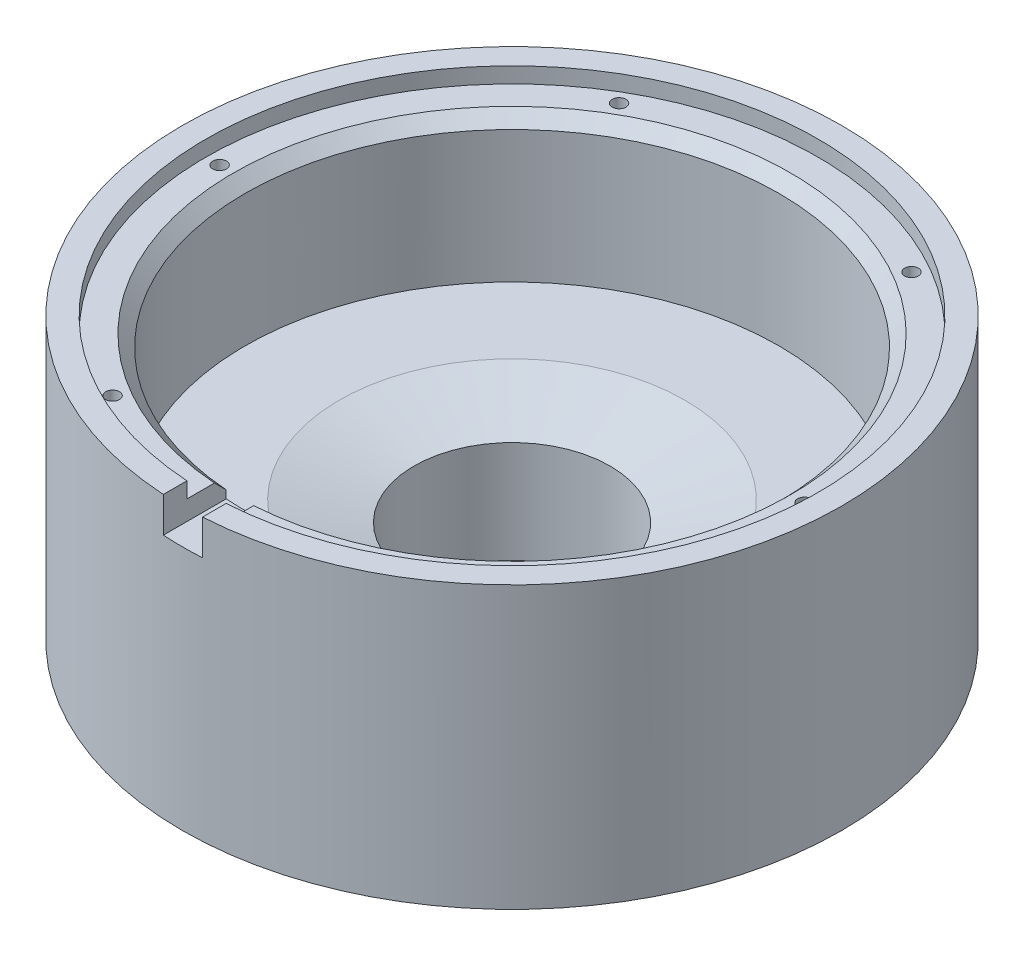
SolidWorks part; units mm, degrees
material "1060 Alloy"
ref_plane "Front Plane" through (0, 0, 0) normal (0, 0, 1) x (1, 0, 0)
ref_plane "Top Plane" through (0, 0, 0) normal (0, 1, 0) x (1, 0, 0)
ref_plane "Right Plane" through (0, 0, 0) normal (1, 0, 0) x (0, 0, -1)
sketch "Sketch7" plane through (0, 0, 0) normal (0, 0, 1) x (1, 0, 0)
  line L0 (0, -30.2319) -> (0, 30.2319) construction
  line L1 (-42.0375, 21.59) -> (-39.0375, 21.59)
  line L2 (-39.0375, 21.59) -> (-39.0375, 19.59)
  line L3 (-39.0375, 19.59) -> (-34.0375, 19.59)
  line L4 (-34.0375, 19.59) -> (-34.0375, 1.25)
  line L7 (-22.0375, 1.25) -> (-34.0375, 1.25)
  line L8 (-12.5, -1.25) -> (-12.5, -14.25)
  line L9 (-12.5, -14.25) -> (-42.0375, -14.25)
  line L10 (-42.0375, -14.25) -> (-42.0375, 21.59)
  line L11 (-17.2688, 0) -> (0, 0) construction
  line L12 (-22.0375, 1.25) -> (-12.5, -1.25)
  point P3 (0, 0)
  point P4 (0, 0)
  point P11 (-10.5839, 0)
  point P12 (0, 0)
  point P18 (0, 0)
  point P19 (-17.2688, 0)
  point P20 (-36.5375, 19.59)
  dimension "D1" = 3
  dimension "D2" = 2
  dimension "D3" = 5
  dimension "D4" = 34.0375
  dimension "D8" = 12
  dimension "D6" = 13
  dimension "D9" = 12.5
  dimension "D5" = 18.34
  dimension "D7" = 2.5
revolve "Base Motor Housing" add sketch "Sketch7" angle 360 about L0
sketch "Sketch8" plane through (0, 21.59, 0) normal (0, 1, 0) x (1, 0, 0)
  line L0 (0, 0) -> (0, -42.0375) construction
  line L1 (-2.5, -42.0375) -> (2.5, -42.0375)
  line L2 (-2.5, -42.0375) -> (-2.5, -33.9456)
  line L3 (-2.5, -33.9456) -> (2.5, -33.9456)
  line L4 (2.5, -42.0375) -> (2.5, -33.9456)
  circle A0 centre (0, 0) radius 42.0375 construction
  circle A1 centre (0, 0) radius 34.0375 construction
  point P10 (0, -42.0375)
  dimension "D1" = 5
extrude "Wire Hole" cut sketch "Sketch8" against normal offset from surface (4.5 mm away) 2.5 up to face at (0, 19.59, -39.0375)
chamfer "Chamfer1" distance 1.5 angle 45 1 edges at (0, 19.59, -34.0375)
sketch "Sketch9" plane through (0, 19.59, 0) normal (0, 1, 0) x (1, 0, 0)
  line L0 (-35.5375, 0) -> (-39.0375, 0) construction
  line L2 (-2.5, -35.4495) -> (-2.5, -33.9456)
  line L3 (2.5, -33.9456) -> (2.5, -35.4495)
  circle A0 centre (0, 0) radius 34.0375 construction
  circle A1 centre (0, 0) radius 34.0375 construction
  circle A2 centre (0, 0) radius 37.2875 construction
  circle A3 centre (-37.2875, 0) radius 0.875
  circle A4 centre (-18.6438, 32.2919) radius 0.875
  circle A5 centre (18.6437, 32.2919) radius 0.875
  circle A6 centre (37.2875, 0) radius 0.875
  circle A7 centre (18.6438, -32.2919) radius 0.875
  circle A8 centre (-18.6437, -32.2919) radius 0.875
  arc A9 (2.5, -38.9574) -> (-2.5, -38.9574) centre (0, 0) ccw construction
  arc A10 (2.5, -38.9574) -> (-2.5, -38.9574) centre (0, 0) ccw construction
  arc A11 (2.5, -33.9456) -> (-2.5, -33.9456) centre (0, 0) ccw
  arc A12 (2.5, -35.4495) -> (-2.5, -35.4495) centre (0, 0) ccw
  arc A14 (2.5, -35.4495) -> (-2.5, -35.4495) centre (0, 0) ccw construction
  point P21 (0, 0)
  point P31 (-37.2875, 0)
  dimension "D2" = 1.75
  dimension "D3" = 6
extrude "Front-Holes" cut sketch "Sketch9" against normal blind 6
sketch "Sketch10" plane through (0, -14.25, 0) normal (0, -1, 0) x (1, 0, 0)
  line L0 (-12.5, 0) -> (-42.0375, 0) construction
  circle A2 centre (0, 0) radius 42.0375 construction
  circle A3 centre (0, 0) radius 42.0375 construction
  circle A4 centre (-27.2687, 0) radius 2.875
  circle A5 centre (-13.6344, 23.6154) radius 2.875
  circle A6 centre (13.6344, 23.6154) radius 2.875
  circle A7 centre (27.2687, 0) radius 2.875
  circle A8 centre (13.6344, -23.6154) radius 2.875
  circle A9 centre (-13.6344, -23.6154) radius 2.875
  circle A10 centre (0, 0) radius 27.2687 construction
  circle A11 centre (0, 0) radius 12.5 construction
  circle A12 centre (0, 0) radius 12.5 construction
  point P12 (0, 0)
  point P22 (0, 0)
  point P24 (0, 0)
  point P25 (0, 0)
  dimension "D1" = 5.75
  dimension "D2" = 6
extrude "Back-Holes" cut sketch "Sketch10" against normal blind 8
equation "\"D2@Sketch9\"=\"Back_mount_hole\""
equation "\"Stator_OD\"= 68'No Tolerance given"
equation "\"D4@Sketch7\"= 1 / 2 * \"Stator_OD\" + \"Stator_Gap\""
equation "\"A\"=18.34"
equation "\"Rotor_ID\"= 34'No Tolerance Given"
equation "\"back_bearing_Thickness\"= 8'randomish, thinnest off mcmaster"
equation "\"D8@Sketch7\"=1/2*(\"Stator_OD\"-\"Rotor_ID\")-5"
equation "\"D6@Sketch7\"=\"back_bearing_Thickness\"+5"
equation "\"back_bearing_OD\"= 25'currently non-sense"
equation "\"D9@Sketch7\"=\"back_bearing_OD\"*1/2"
equation "\"D5@Sketch7\"=\"A\""
equation "\"Stator_Gap\"= 0.0375'+- 0.0125 (From 1.3.3.1 Kollmorgen manual)"
equation "\"Back_mount_hole\"= 1.75'To be tapped to M2 (USE LOCKTITE)"
equation "\"D1@Back-Holes\" = \"back_bearing_Thickness\""
equation "\"facePlate_Mount_Hole\"= 5.75'To be tapped to M6"
equation "\"D1@Sketch10\"=\"facePlate_Mount_Hole\""
equation "\"final_shaftD\"= 8'NEMA 23 shaft diameter. Should fit with harmonic?"
equation "\"back_bearing_ID\"= 15'Random number"
equation "\"final_shaftL\"= 50'random length. Idk"
equation "\"back_bearing_IDOD\"= 20'Random number, OD of the inner bearing ring"
equation "\"rotor_shaftD\"= \"Rotor_ID\" - (0.0185)*2'+-0.0065 (from manual)"
equation "\"front_bearing_ID\"= 12'random"
equation "\"front_bearing_OD\"= 20'random"
equation "\"front_bearing_IDOD\"= 14'random"
equation "\"front_bearing_Thickness\"= 5'randomish, thinnest off mcmaster"
equation "\"rotor_thickness\"= 2.4'measured off CAD"
equation "\"rotor_height\"= 14.8'measured off CAD"
